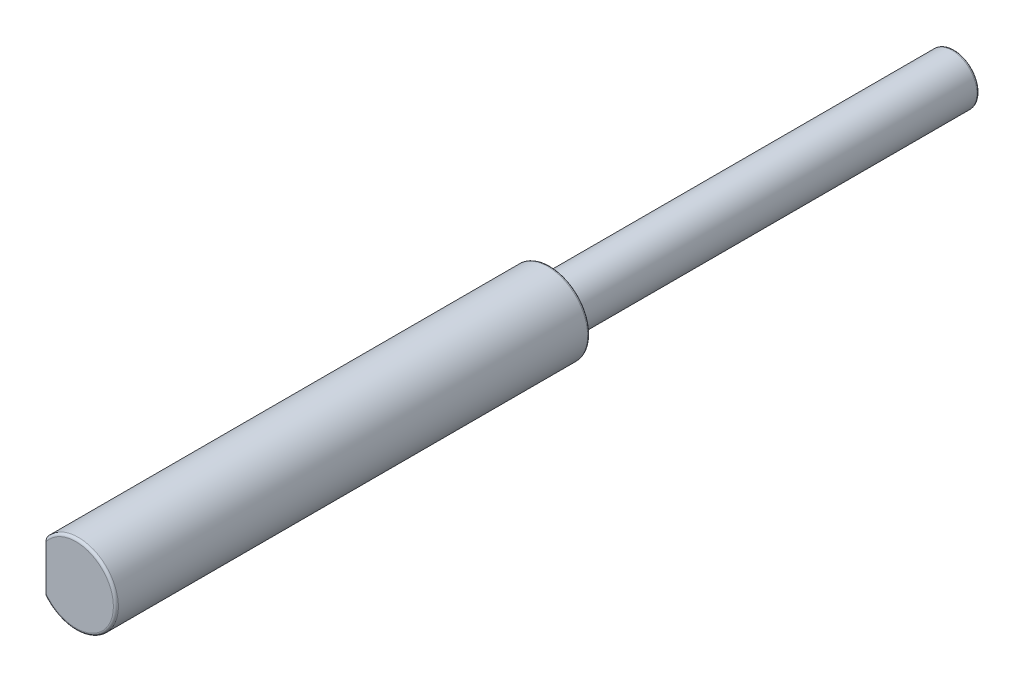
SolidWorks part; units mm, degrees
material "Acero aleado"
ref_plane "Plane1" through (0, 0, 0) normal (0, 0, 1) x (1, 0, 0)
ref_plane "Plane2" through (0, 0, 0) normal (0, 1, 0) x (1, 0, 0)
ref_plane "Plane3" through (0, 0, 0) normal (1, 0, 0) x (0, 0, -1)
sketch "Sketch1" plane through (0, 0, 0) normal (0, 0, 1) x (1, 0, 0)
  circle A0 centre (0, 0) radius 2.5
  dimension "D1" = 5
extrude "Extrude1" add sketch "Sketch1" along normal blind 40.5
sketch "Sketch3" plane through (0, 0, 40.5) normal (0, 0, 1) x (1, 0, 0)
  circle A0 centre (0, 0) radius 4
  dimension "D1" = 8
extrude "Boss-Extrude1" add sketch "Sketch3" along normal blind 47.5 contours A0
fillet "Fillet1" radius 0.25 3 edges at (4, 0, 88) (4, 0, 40.5) (2.5, 0, 0)
sketch "Sketch2" plane through (0, 0, 0) normal (0, 1, 0) x (1, 0, 0)
  line L0 (-3, -88) -> (-5, -88)
  line L2 (-5, -88) -> (-5, -73)
  line L3 (-5, -73) -> (-4, -73)
  line L4 (-3, -74) -> (-3, -88)
  line L5 (0, -88) -> (0, -71.8978) construction
  line L6 (-3.75, -88) -> (3.75, -88) construction
  arc A0 (-4, -73) -> (-3, -74) centre (-4, -74) cw
  dimension "D3" = 1
  dimension "D1" = 3
  dimension "D2" = 15
  dimension "D4" = 2
extrude "Cut-Extrude1" cut sketch "Sketch2" against normal blind 3 and the other way blind 3
